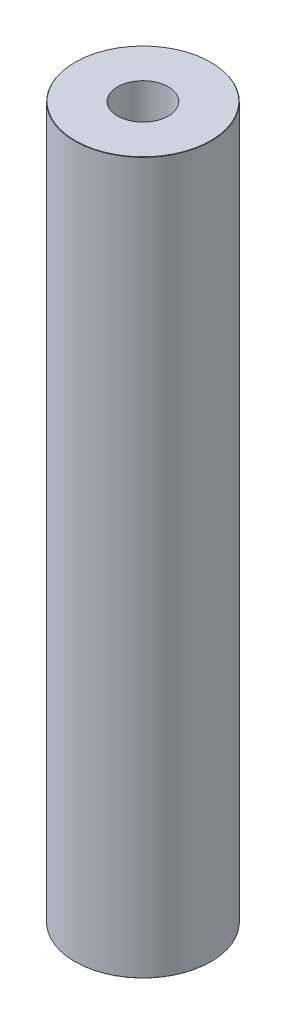
SolidWorks part; units mm, degrees
ref_plane "Front Plane" through (0, 0, 0) normal (0, 0, 1) x (1, 0, 0)
ref_plane "Top Plane" through (0, 0, 0) normal (0, 1, 0) x (1, 0, 0)
ref_plane "Right Plane" through (0, 0, 0) normal (1, 0, 0) x (0, 0, -1)
sketch "Sketch1" plane through (0, 0, 0) normal (0, 1, 0) x (1, 0, 0)
  circle A0 centre (0, 0) radius 57.5
  dimension "SHAFT_OD" = 115
extrude "Boss-Extrude1" add sketch "Sketch1" along normal blind 600
sketch "Sketch2" plane through (0, 0, 0) normal (0, 1, 0) x (1, 0, 0)
  circle A0 centre (0, 0) radius 21.407
  dimension "BORE_D" = 42.814
extrude "Cut-Extrude1" cut sketch "Sketch2" along normal through all
chamfer "Chamfer1" distance 0.2492 angle 45 2 edges at (0, 600, 57.5) (0, 0, 57.5)
